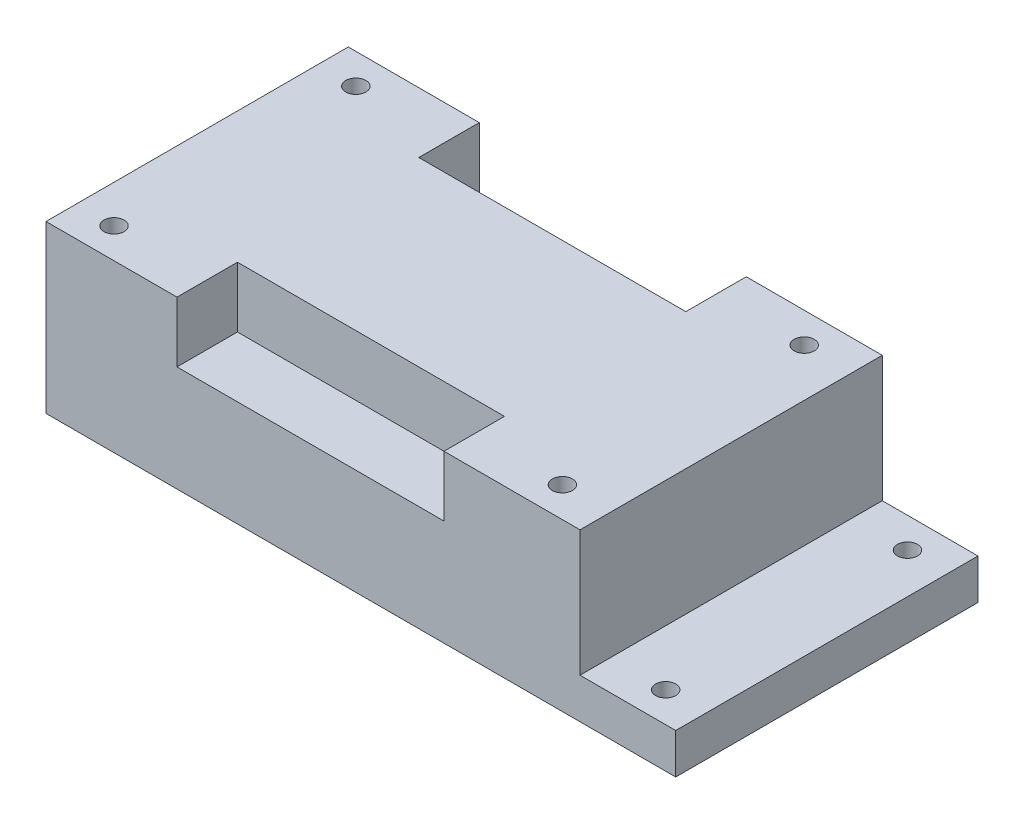
SolidWorks part; units mm, degrees
ref_plane "Front Plane" through (0, 0, 0) normal (0, 0, 1) x (1, 0, 0)
ref_plane "Top Plane" through (0, 0, 0) normal (0, 1, 0) x (1, 0, 0)
ref_plane "Right Plane" through (0, 0, 0) normal (1, 0, 0) x (0, 0, -1)
sketch "Sketch1" plane through (0, 0, 0) normal (0, 1, 0) x (1, 0, 0)
  line L0 (43.5, 30) -> (43.5, -30)
  line L1 (-62.5, -30) -> (62.5, -30)
  line L2 (-62.5, -30) -> (-62.5, 30)
  line L3 (-62.5, 30) -> (62.5, 30)
  line L4 (62.5, -30) -> (62.5, 30)
  line L5 (-62.5, -30) -> (62.5, 30) construction
  line L6 (-62.5, 30) -> (62.5, -30) construction
  line L7 (-36.5, -30) -> (-36.5, -18)
  line L8 (-36.5, -18) -> (16.5, -18)
  line L9 (16.5, -18) -> (16.5, -30)
  line L10 (-36.5, 30) -> (-36.5, 18)
  line L11 (-36.5, 18) -> (16.5, 18)
  line L12 (16.5, 18) -> (16.5, 30)
  line L13 (54.5, 30) -> (54.5, -30)
  circle A0 centre (54.5, -24) radius 2
  circle A1 centre (54.5, 24) radius 2
  circle A2 centre (34, -24) radius 2
  circle A3 centre (-55, -24) radius 2
  circle A4 centre (-55, 24) radius 2
  circle A5 centre (34, 24) radius 2
  point P0 (0, 0)
  point P30 (0, 0)
  point P31 (0, 0)
  point P32 (0, 0)
  point P33 (0, 0)
  point P34 (-49.7518, 24)
  point P35 (0, 0)
  point P36 (-49.2219, 23.6265)
  point P37 (-45.6746, 24)
  dimension "D13" = 4
  dimension "D14" = 4
  dimension "D15" = 4
  dimension "D16" = 4
  dimension "D17" = 4
  dimension "D18" = 4
  dimension "D1" = 125
  dimension "D2" = 60
  dimension "D3" = 19
  dimension "D4" = 26
  dimension "D5" = 26
  dimension "D6" = 53
  dimension "D7" = 53
  dimension "D8" = 12
  dimension "D9" = 12
  dimension "D10" = 11
  dimension "D11" = 6
  dimension "D12" = 6
  dimension "D19" = 20.5
  dimension "D20" = 89
extrude "Boss-Extrude1" add sketch "Sketch1" along normal blind 33 contours L12 L11 L10 L3 L2 L1 L7 L8 L9 L0 region at (-9.3638, 0, 0)
extrude "Boss-Extrude2" add sketch "Sketch1<3>" along normal blind 21 contours L9 L8 L7 L1 | L11 L12 L3 L10 region at (-10, 0, -24) region at (-10, 0, 24)
sketch "Sketch1<3>" plane through (0, 0, 0) normal (0, 1, 0) x (1, 0, 0) same geometry as "Sketch1"
extrude "Boss-Extrude3" add sketch "Sketch1<4>" along normal blind 8 contours A1 L13 L3 L0 L1 A0 | A1 L13 A0 L1 L4 L3 region at (48.9097, 0, 0) region at (58.5847, 0, 0)
sketch "Sketch1<4>" plane through (0, 0, 0) normal (0, 1, 0) x (1, 0, 0) same geometry as "Sketch1"
